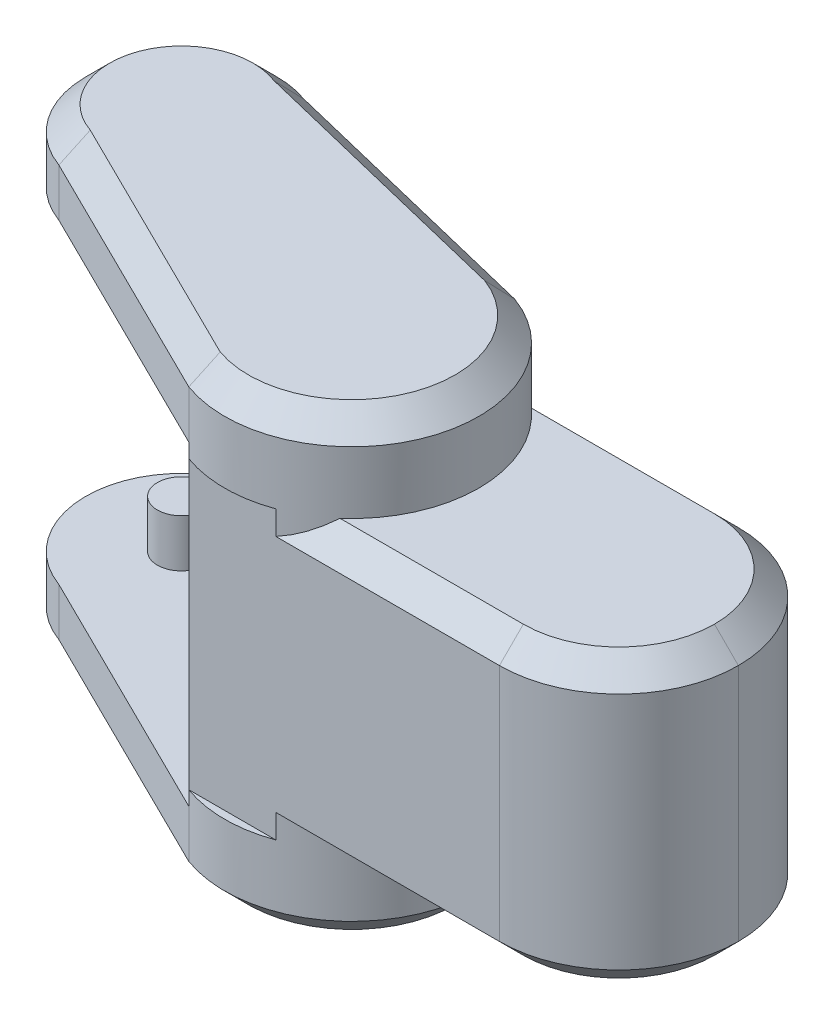
SolidWorks part; units mm, degrees
ref_plane "Front Plane" through (0, 0, 0) normal (0, 0, 1) x (1, 0, 0)
ref_plane "Top Plane" through (0, 0, 0) normal (0, 1, 0) x (1, 0, 0)
ref_plane "Right Plane" through (0, 0, 0) normal (1, 0, 0) x (0, 0, -1)
sketch "Sketch1" plane through (0, 0, 0) normal (0, 1, 0) x (1, 0, 0)
  line L0 (0, 0) -> (18.1985, 50)
  line L1 (18.1985, 50) -> (90, 50)
  line L2 (90, 50) -> (90, 0)
  line L3 (90, 0) -> (0, 0)
  dimension "D1" = 50
  dimension "D2" = 90
  dimension "D3" = 70
extrude "Boss-Extrude1" add sketch "Sketch1" along normal blind 60
fillet "Fillet1" radius 25 2 edges at (90, 30, 0) (90, 30, -50)
ref_plane "Plane1" through (0, 78, 0) normal (0, 1, 0) x (1, 0, 0)
sketch "Sketch2" plane through (0, 78, 0) normal (0, 1, 0) x (1, 0, 0)
  line L5 (18.1985, 50) -> (0, 0)
  line L8 (18.1985, 50) -> (0, 0) construction
  arc A1 (18.1985, 50) -> (0, 0) centre (9.0993, 25) cw
  point P6 (0, 0)
extrude "Boss-Extrude2" add sketch "Sketch2" against normal up to surface (18 mm away) up to face at (49.7108, 60, -25)
sketch "Sketch3" plane through (0, 78, 0) normal (0, 1, 0) x (1, 0, 0)
  line L6 (18.1985, 50) -> (0, 0) construction
  line L8 (18.1985, 50) -> (0, 0)
  line L10 (-40.1181, 64.1972) -> (18.1985, 50)
  line L11 (-53.7989, 26.6095) -> (0, 0)
  arc A2 (0, 0) -> (18.1985, 50) centre (9.0993, 25) ccw construction
  arc A4 (-40.1181, 64.1972) -> (-53.7989, 26.6095) centre (-46.9585, 45.4033) ccw
  dimension "D1" = 20
ref_plane "Plane2" through (0, 30, 0) normal (0, 1, 0) x (1, 0, 0)
extrude "Boss-Extrude4" add sketch "Sketch3" against normal blind 15 contours L11 L8 L10 A4
ref_plane "Plane3" through (0, 30, 0) normal (0, -1, 0) x (-1, 0, 0)
sketch "Sketch4" plane through (0, 0, 0) normal (0, -1, 0) x (1, 0, 0)
  line L0 (65, -50) -> (18.1985, -50) construction
  line L1 (18.1985, -50) -> (0, 0)
  arc A0 (0, 0) -> (18.1985, -50) centre (9.0993, -25) cw
extrude "Boss-Extrude5" add sketch "Sketch4" along normal blind 18
sketch "Sketch5" plane through (0, -18, 0) normal (0, -1, 0) x (1, 0, 0)
  line L0 (-53.7989, -26.6095) -> (0, 0)
  line L1 (0, 0) -> (18.1985, -50)
  line L2 (18.1985, -50) -> (-40.1181, -64.1972)
  arc A0 (-53.7989, -26.6095) -> (-40.1181, -64.1972) centre (-46.9585, -45.4033) ccw
  arc A1 (-53.7989, -26.6095) -> (-40.1181, -64.1972) centre (-46.9585, -45.4033) ccw construction
extrude "Boss-Extrude6" add sketch "Sketch5" against normal blind 15
chamfer "Chamfer1" distance 5 angle 45 16 edges at (-26.8994, 78, -13.3047) (-65.7523, 78, -52.2437) (-10.9598, 78, -57.0986) (34.0993, 78, -15.9007) (41.5993, 0, -50) (82.6777, 0, -42.6777) (82.6777, 0, -7.3223) (41.5993, 0, 0) (41.5993, 60, -50) (82.6777, 60, -42.6777) (82.6777, 60, -7.3223) (41.5993, 60, 0) (34.0993, -18, -15.9007) (-10.9598, -18, -57.0986) (-65.7523, -18, -52.2437) (-26.8994, -18, -13.3047)
sketch "Sketch6" plane through (0, 0, 0) normal (0, -1, 0) x (-1, 0, 0)
  circle A0 centre (-65, 25) radius 5
  dimension "D1" = 10
extrude "Cut-Extrude1" cut sketch "Sketch6" against normal blind 10
sketch "Sketch7" plane through (0, -3, 0) normal (0, 1, 0) x (1, 0, 0)
  circle A0 centre (-46.9585, 45.4033) radius 5
  dimension "D1" = 10
extrude "Boss-Extrude7" add sketch "Sketch7" along normal blind 10
